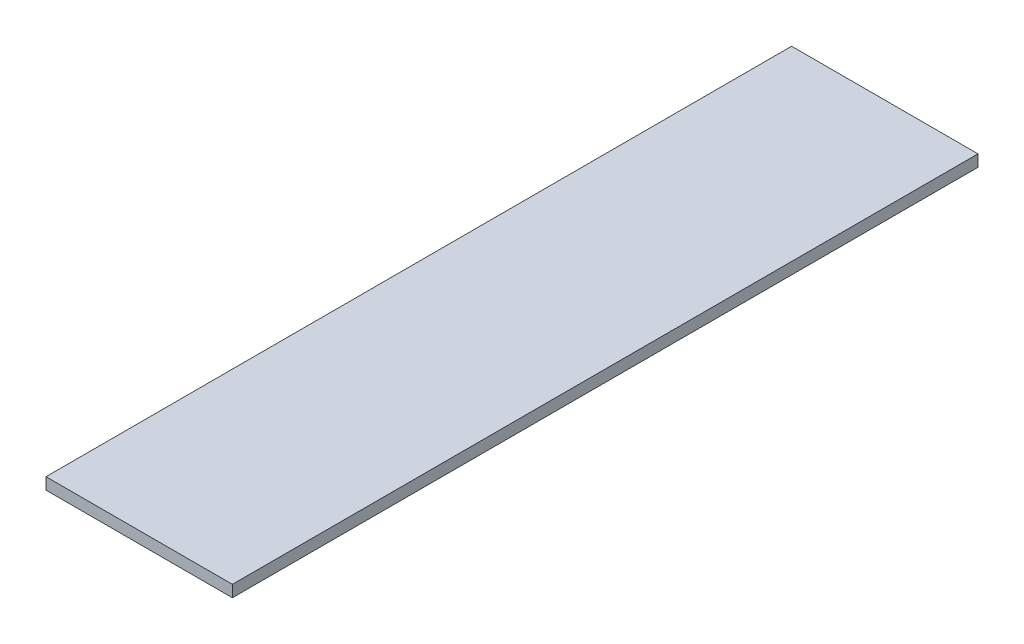
SolidWorks part; units mm, degrees
ref_plane "Front" through (0, 0, 0) normal (0, 0, 1) x (1, 0, 0)
ref_plane "Top" through (0, 0, 0) normal (0, 1, 0) x (1, 0, 0)
ref_plane "Right" through (0, 0, 0) normal (1, 0, 0) x (0, 0, -1)
sketch "Sketch1" plane through (0, 0, 0) normal (0, 1, 0) x (1, 0, 0)
  line L1 (0, 0) -> (50.8, 0)
  line L2 (0, 0) -> (0, 203.2)
  line L3 (0, 203.2) -> (50.8, 203.2)
  line L4 (50.8, 0) -> (50.8, 203.2)
  dimension "D1" = 50.8
  dimension "D2" = 203.2
extrude "Boss-Extrude1" add sketch "Sketch1" along normal blind 3.175
